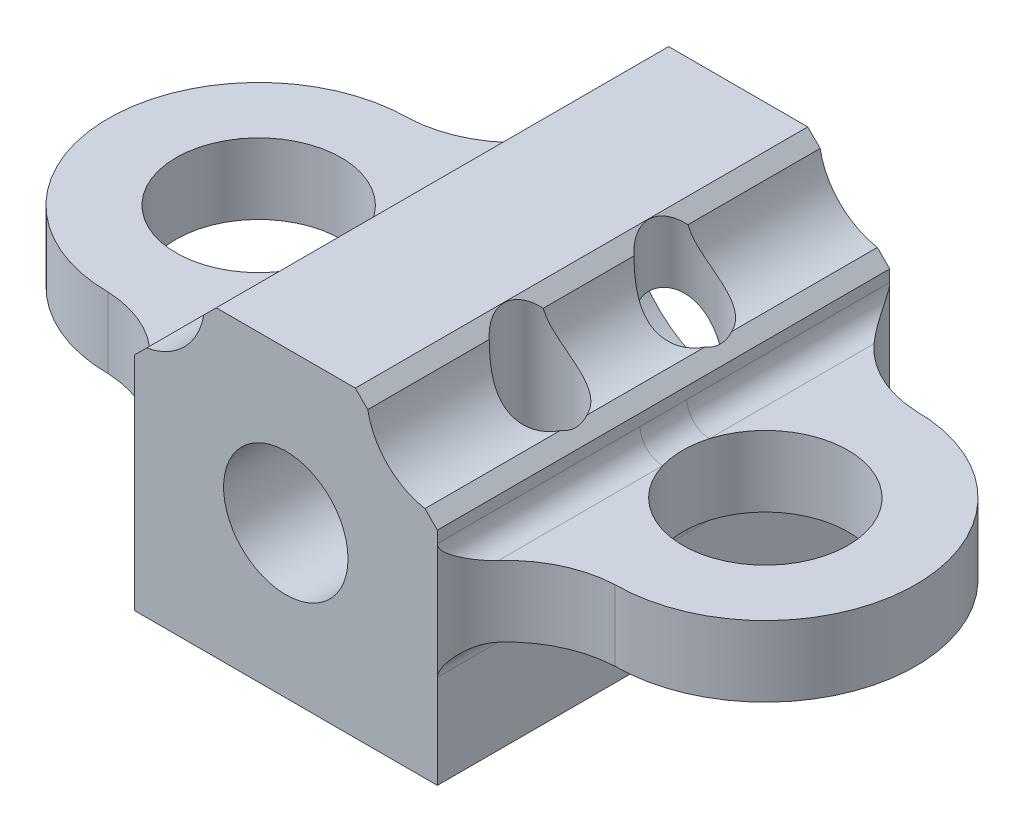
SolidWorks part; units mm, degrees
ref_plane "Front Plane" through (0, 0, 0) normal (0, 0, 1) x (1, 0, 0)
ref_plane "Top Plane" through (0, 0, 0) normal (0, 1, 0) x (1, 0, 0)
ref_plane "Right Plane" through (0, 0, 0) normal (1, 0, 0) x (0, 0, -1)
sketch "Sketch1" plane through (0, 0, 0) normal (0, 0, 1) x (1, 0, 0)
  line L0 (0, 0) -> (0, 69.4209) construction
  line L1 (8.509, 17.018) -> (-8.509, 17.018)
  line L2 (-8.509, 17.018) -> (-8.509, 0)
  line L3 (-8.509, 0) -> (8.509, 0)
  line L4 (8.509, 17.018) -> (8.509, 0)
  point P8 (0, 17.018)
  dimension "D1" = 17.018
  dimension "D2" = 17.018
extrude "Boss-Extrude1" add sketch "Sketch1" along normal blind 25.4
ref_plane "Plane1" through (0, 8.509, 0) normal (0, 1, 0) x (1, 0, 0)
sketch "Sketch2" plane through (0, 0, 0) normal (1, 0, 0) x (0, 0, -1)
  line L0 (-25.4, 8.509) -> (1.0345, 8.509) construction
  line L1 (-25.4, 0) -> (-25.4, 17.018) construction
  line L2 (-12.7, 14.859) -> (0, 14.859)
  line L3 (-12.7, 14.859) -> (-12.7, 12.0015)
  line L4 (-12.7, 12.0015) -> (-25.4, 12.0015)
  line L5 (-25.4, 12.0015) -> (-25.4, 8.509)
  line L6 (-25.4, 17.018) -> (0, 17.018) construction
  line L7 (-25.4, 8.509) -> (-12.1828, 8.509)
  line L9 (0, 0) -> (0, 17.018) construction
  line L10 (-12.1828, 8.509) -> (0, 8.509)
  line L11 (0, 8.509) -> (0, 14.859)
  dimension "D1" = 2.159
  dimension "D2" = 6.985
  dimension "D3" = 12.7
revolve "Cut-Revolve1" cut sketch "Sketch2" angle 360 about L7
sketch "Sketch4" plane through (0, 0, 0) normal (0, -1, 0) x (1, 0, 0)
  line L1 (-6, 17.0663) -> (6, 17.0663) construction
  line L2 (-6, 17.0663) -> (-6, 9.0663) construction
  line L3 (-6, 9.0663) -> (6, 9.0663) construction
  line L4 (6, 17.0663) -> (6, 9.0663) construction
  line L5 (-6, 17.0663) -> (6, 9.0663) construction
  line L6 (-6, 9.0663) -> (6, 17.0663) construction
  line L15 (-8.509, 25.4) -> (8.509, 25.4) construction
  circle A0 centre (-6, 17.0663) radius 1.016
  circle A1 centre (5.938, 17.0663) radius 1.016
  circle A2 centre (5.938, 8.9383) radius 1.016
  circle A3 centre (-6, 8.9383) radius 1.016
  point P0 (0, 13.0663)
  dimension "D3" = 2.032
  dimension "D1" = 12
  dimension "D2" = 8
  dimension "D6" = 8.3337
  dimension "D4" = 2
  dimension "D5" = 2
extrude "Cut-Extrude2" cut sketch "Sketch4" against normal through all
sketch "Sketch5" plane through (0, 8.509, 0) normal (0, 1, 0) x (1, 0, 0)
  line L1 (-14.1338, -12.7) -> (28.118, -12.7) construction
  line L5 (14.224, -12.7) -> (20.4143, -25.9751) construction
  line L8 (8.509, 0) -> (8.509, -25.4)
  line L10 (0, -25.4) -> (0, 11.748) construction
  line L11 (8.509, -25.4) -> (-8.509, -25.4) construction
  line L12 (14.224, 13.3789) -> (14.224, -38.7789) construction
  arc A0 (14.224, -4.2545) -> (14.224, -21.1455) centre (14.224, -12.7) cw
  circle A1 centre (14.224, -12.7) radius 4.6355
  arc A2 (14.224, -21.1455) -> (8.509, -25.4) centre (14.5055, -27.4893) ccw
  arc A3 (14.224, -4.2545) -> (8.509, 0) centre (14.5055, 2.0893) cw
  dimension "D2" = 9.271
  dimension "D4" = 3.81
  dimension "D3" = 6.35
  dimension "D1" = 5.715
  dimension "D5" = 25
extrude "Boss-Extrude2" add sketch "Sketch5" against normal blind 1.9844 and the other way blind 1.9844
mirror "Mirror1" about plane through (0, 0, 0) normal (1, 0, 0) of "Boss-Extrude2"
sketch "Sketch7" plane through (0, 0, 25.4) normal (0, 0, 1) x (1, 0, 0)
  line L0 (0, 19.0675) -> (0, -3.3693) construction
  circle A0 centre (8.509, 17.018) radius 3.9687
  circle A1 centre (-8.509, 17.018) radius 3.9687
  dimension "D1" = 7.9375
extrude "Cut-Extrude3" cut sketch "Sketch7" against normal through all
fillet "Fillet3" radius 1.27 4 edges
chamfer "Chamfer1" distance 0.635 angle 45 4 edges at (8.509, 13.0492, 12.7) (4.5402, 17.018, 12.7) (-4.5402, 17.018, 12.7) (-8.509, 13.0492, 12.7)
sketch "Sketch10" plane through (0, 17.018, 0) normal (0, 1, 0) x (1, 0, 0)
  line L0 (-0.031, -8.9383) -> (-0.031, -21.1529) construction
  line L1 (-6, -8.9383) -> (5.938, -8.9383) construction
  line L2 (-6, -8.9383) -> (-6, -17.0663) construction
  line L3 (-6, -17.0663) -> (5.938, -17.0663) construction
  line L4 (5.938, -8.9383) -> (5.938, -17.0663) construction
  line L5 (5.938, -13.0023) -> (-11.7995, -13.0023) construction
  circle A0 centre (5.938, -8.9383) radius 2.0193
  circle A1 centre (-6, -8.9383) radius 2.0193
  circle A2 centre (5.938, -17.0663) radius 2.0193
  circle A3 centre (-6, -17.0663) radius 2.0193
  dimension "D1" = 4.0386
extrude "Cut-Extrude6" cut sketch "Sketch10" against normal blind 13.97
sketch "Sketch11" plane through (0, 17.018, 0) normal (0, 1, 0) x (1, 0, 0)
  line L0 (5.938, -8.9383) -> (5.938, -28.9543) construction
ref_plane "Plane2" through (5.938, 0, 0) normal (1, 0, 0) x (0, 0, -1)
ref_plane "Plane3" through (0, 8.509, 0) normal (0, 1, 0) x (1, 0, 0)
